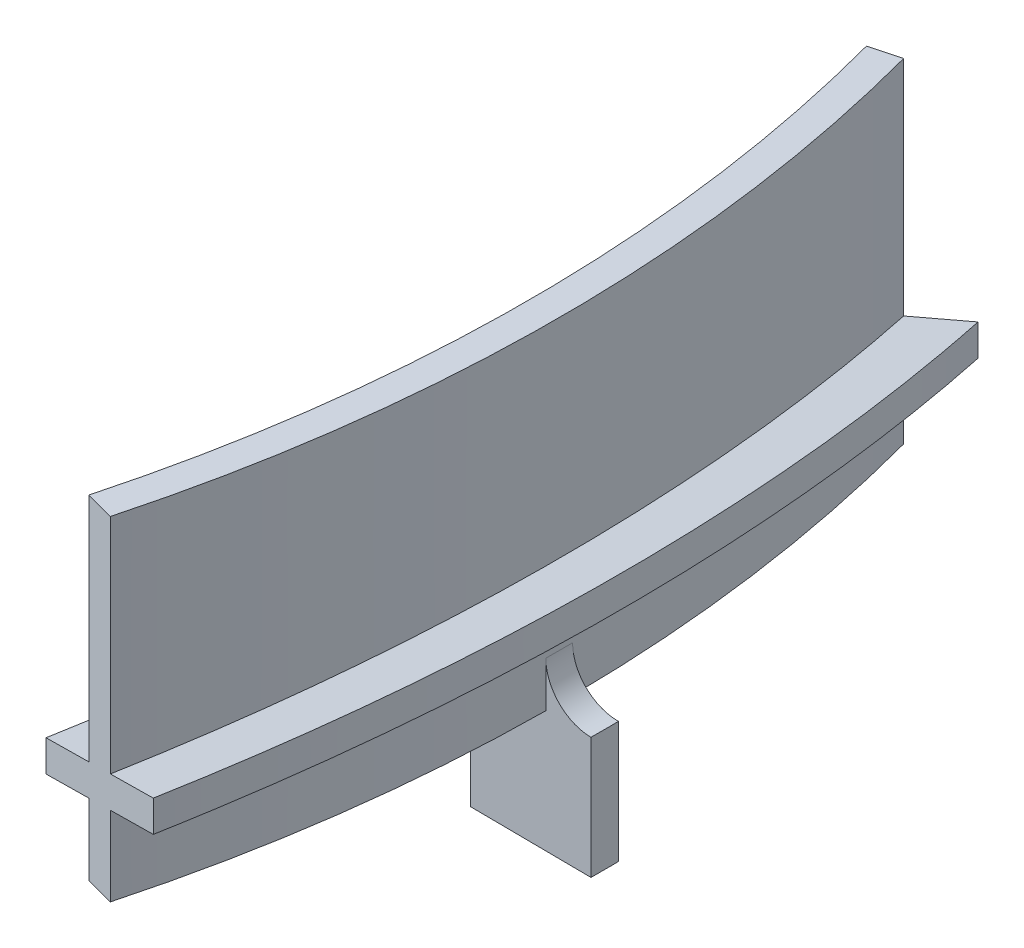
SolidWorks part; units mm, degrees
ref_plane "Front Plane" through (0, 0, 0) normal (0, 0, 1) x (1, 0, 0)
ref_plane "Top Plane" through (0, 0, 0) normal (0, 1, 0) x (1, 0, 0)
ref_plane "Right Plane" through (0, 0, 0) normal (1, 0, 0) x (0, 0, -1)
sketch "Sketch1" plane through (0, 0, 0) normal (0, 0, 1) x (1, 0, 0)
  line L13 (101, 16) -> (99, 16)
  line L14 (101, 16) -> (101, -6)
  line L15 (101, -6) -> (99, -6)
  line L16 (99, 16) -> (99, -6)
  point P4 (100, 16)
  dimension "D1" = 22
  dimension "D2" = 2
  dimension "D3" = 100
  dimension "D4" = 6
ref_axis "Axis1" through (0, 12.85, 0) along (0, -1, 0)
revolve "Revolve1" add sketch "Sketch1" angle 30 mid plane about axis through (0, 12.85, 0) along (0, -1, 0)
ref_axis "Axis2" through (0, 0, -28.7548) along (0, 0, 1)
ref_plane "Plane2" through (0, 0, 0) normal (-0.2588, 0.9659, 0) x (0, 0, 1)
ref_axis "Axis4" through (0, 0, 0) along (-0.2588, 0.9659, 0)
sketch "Sketch13" plane through (0, 0, 0) normal (-0.2588, 0, 0.9659) x (0.9659, 0, 0.2588)
  line L0 (80.6815, -4.1411) -> (119.3185, 6.2117)
  line L1 (119.3185, 6.2117) -> (119.3185, 4.1411)
  line L2 (119.3185, 4.1411) -> (80.6815, -6.2117)
  line L3 (80.6815, -6.2117) -> (80.6815, -4.1411)
  line L4 (80.6815, -5.1764) -> (119.3185, 5.1764) construction
  line L5 (100, 1.0353) -> (100, -1.0353) construction
  line L6 (101, 16) -> (99, 16) construction
  point P8 (100, 0)
  point P11 (100, 16)
  dimension "D1" = 75
  dimension "D2" = 40
  dimension "D3" = 2
extrude "Boss-Extrude2" add sketch "Sketch13" along direction (0, 0, 1) on the side against the normal blind 57
sketch "Sketch15" plane through (0, 0, 0) normal (0, 1, 0) x (1, 0, 0)
  line L0 (91.43, 25.7982) -> (101.0543, 28.5138) construction
  line L1 (0, 0) -> (101.4222, 27.176)
  line L2 (0, 0) -> (101.4222, -27.176)
  line L3 (0, 0) -> (105, 0) construction
  circle A0 centre (0, 0) radius 100 construction
  circle A1 centre (0, 0) radius 95
  circle A2 centre (0, 0) radius 105
  circle A3 centre (0, 0) radius 211.9463
  point P7 (96.2421, 27.156)
  dimension "D1" = 200
  dimension "D2" = 10
  dimension "D3" = 30
extrude "Cut-Extrude1" cut sketch "Sketch15" against normal through all both and the other way through all contours A3 A2 | L1 A2 L2 A1 | L2 A1 L1 | L1 A1 L2 region at (-5.692, 0, 0) region at (62.6123, 0, 0) region at (-97.9447, 0, 0) region at (-205.9515, 0, 0)
sketch "Sketch16" plane through (0, 0, 0) normal (0, 0, 1) x (1, 0, 0)
  line L1 (96, -6) -> (104, -6)
  line L2 (96, -6) -> (96, -14)
  line L3 (96, -14) -> (104, -14)
  line L4 (104, -6) -> (104, -14)
  line L5 (97.5585, -6) -> (101, -6) construction
  line L6 (0, 12.85) -> (0, -5.85) construction
  point P4 (100, -14)
  dimension "D1" = 8
  dimension "D2" = 100
revolve "Revolve2" add sketch "Sketch16" angle 1 mid plane about axis through (0, 12.85, 0) along (0, -1, 0)
fillet "Fillet2" radius 3 2 edges at (99, -6, 0) (101, -6, 0)
equation "\"slope_angle\"= 15deg"
equation "\"gate_height\"= 10mm"
equation "\"sweep_angle\"= 30deg"
equation "\"gate_thickness\"= 2mm"
equation "\"gate_cross_width\"= 10mm"
equation "\"gate_radius\"= 100mm"
equation "\"D1@Sketch1\"=\"gate_height\"+\"gate_cross_width\"+\"gate_thickness\""
equation "\"D2@Sketch1\"=\"gate_thickness\""
equation "\"D3@Sketch1\"=\"gate_radius\""
equation "\"D1@Sketch13\"= 90 - \"slope_angle\""
equation "\"D2@Sketch13\"=4* \"gate_cross_width\""
equation "\"D3@Sketch13\"=\"gate_thickness\""
equation "\"D1@Sketch15\"=2 *\"gate_radius\""
equation "\"D2@Sketch15\"=\"gate_cross_width\""
equation "\"D3@Sketch15\"=\"sweep_angle\""
equation "\"D4@Sketch1\"=(\"gate_cross_width\" +\"gate_thickness\")/2"
equation "\"D2@Sketch16\"=\"gate_radius\""
